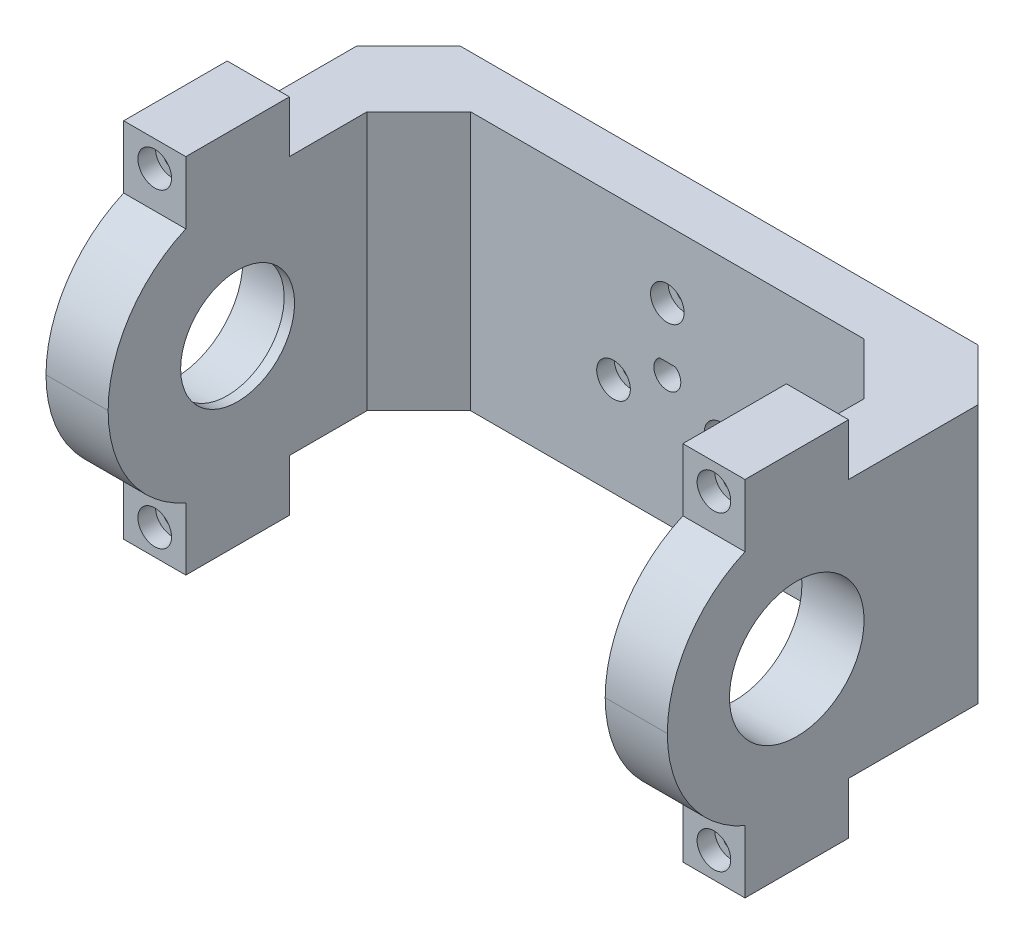
SolidWorks part; units mm, degrees
ref_plane "Ebene vorne" through (0, 0, 0) normal (0, 0, 1) x (1, 0, 0)
ref_plane "Ebene oben" through (0, 0, 0) normal (0, 1, 0) x (1, 0, 0)
ref_plane "Ebene rechts" through (0, 0, 0) normal (1, 0, 0) x (0, 0, -1)
sketch "Skizze1" plane through (0, 0, 0) normal (0, 1, 0) x (1, 0, 0)
  line L0 (-60, 0) -> (60, 0)
  line L5 (0, 0) -> (0, -46.899) construction
  line L6 (-60, 0) -> (-60, -70)
  line L7 (-60, -70) -> (-48, -70)
  line L8 (-48, -70) -> (-48, -10)
  line L9 (-48, -10) -> (48, -10)
  line L10 (48, -10) -> (48, -70)
  line L11 (48, -70) -> (60, -70)
  line L12 (60, -70) -> (60, 0)
  point P4 (0, 0)
  dimension "D1" = 120
  dimension "D2" = 10
  dimension "D3" = 12
  dimension "D4" = 70
extrude "Aufsatz-Linear austragen1" add sketch "Skizze1" along normal mid plane 50
sketch "Skizze2" plane through (0, 0, 0) normal (0, 0, -1) x (-1, 0, 0)
  line L0 (-1.533, 2.1) -> (1.533, 2.1)
  arc A0 (-1.533, 2.1) -> (1.533, 2.1) centre (0, 0) ccw
  dimension "D1" = 5.2
  dimension "D2" = 4.7
extrude "Schnitt-Linear austragen1" cut sketch "Skizze2" against normal blind 20
chamfer "Fase1" distance 10 angle 45 4 edges at (60, 0, 0) (48, 0, 10) (-60, 0, 0) (-48, 0, 10)
fillet "Verrundung1" radius 25 4 edges at (-54, -25, 70) (-54, 25, 70) (54, 25, 70) (54, -25, 70)
sketch "Skizze3" plane through (0, 0, 10) normal (0, 0, 1) x (1, 0, 0)
  line L0 (0, 0) -> (0, 12) construction
  circle A0 centre (0, 12) radius 3.25
  dimension "D2" = 6.5
  dimension "D1" = 12
extrude "Schnitt-Linear austragen2" cut sketch "Skizze3" against normal blind 3.4
sketch "Skizze4" plane through (0, 0, 6.6) normal (0, 0, 1) x (1, 0, 0)
  circle A0 centre (0, 12) radius 1.7
  dimension "D1" = 3.4
extrude "Schnitt-Linear austragen3" cut sketch "Skizze4" against normal up to surface (6.6 mm away) up to face at (0, -0.25, 0)
pattern_circular "Kreismuster1" count 3 over 360 about axis through (0, 0, 20) along (0, 0, -1) of "Schnitt-Linear austragen3", "Schnitt-Linear austragen2"
sketch "Skizze5" plane through (60, 0, 0) normal (1, 0, 0) x (0, 0, -1)
  line L0 (-45, 25) -> (-45, -25) construction
  line L2 (0, 0) -> (-70, 0) construction
  circle A0 centre (-45, 0) radius 13
  arc A2 (-70, 0) -> (-45, -25) centre (-45, 0) ccw construction
  point P5 (-70, 0)
  point P11 (-50, 0)
  dimension "D1" = 26
extrude "Schnitt-Linear austragen4" cut sketch "Skizze5" against normal through all
sketch "Skizze7" plane through (0, 25, 0) normal (0, 1, 0) x (1, 0, 0)
  line L0 (-60, -10) -> (-60, -45) construction
  line L1 (-60, -35) -> (-48, -35)
  line L2 (-60, -35) -> (-60, -55)
  line L3 (-60, -55) -> (-48, -55)
  line L4 (-48, -35) -> (-48, -55)
  line L5 (-48, -70) -> (-48, -45) construction
  line L7 (-62.3385, -45) -> (-41.5692, -45) construction
  line L8 (-60, -45) -> (-48, -45) construction
  point P12 (0, 0)
  dimension "D1" = 20
extrude "Aufsatz-Linear austragen2" add sketch "Skizze7" along normal blind 10 and the other way blind 10
sketch "Skizze9" plane through (0, 0, 35) normal (0, 0, 1) x (1, 0, 0)
  line L0 (-48, 30) -> (-60, 30) construction
  line L1 (-48, 25) -> (-48, 35) construction
  line L2 (-60, 25) -> (-60, 35) construction
  circle A0 centre (-54, 30) radius 1.7
  point P9 (-55, 30)
  dimension "D1" = 3.4
extrude "Schnitt-Linear austragen7" cut sketch "Skizze9" along normal through all
sketch "Skizze8" plane through (0, 0, 55) normal (0, 0, 1) x (1, 0, 0)
  circle A0 centre (-54, 30) radius 3.25
  circle A1 centre (-54, 30) radius 1.7 construction
  point P2 (-55.1693, 29.1455)
  point P3 (-54.6489, 29.8028)
  point P14 (0, 0)
  dimension "D1" = 6.5
extrude "Schnitt-Linear austragen6" cut sketch "Skizze8" against normal blind 3.4
sketch "Skizze10" plane through (-48, 0, 0) normal (-1, 0, 0) x (0, 0, 1)
  circle A0 centre (45, 0) radius 13
  circle A2 centre (45, 0) radius 13 construction
  circle A3 centre (45, 0) radius 11
  point P5 (50, 0)
  dimension "D1" = 22
extrude "Aufsatz-Linear austragen3" add sketch "Skizze10" along normal blind 2
mirror "Spiegeln1" about plane through (0, 0, 0) normal (1, 0, 0) of "Schnitt-Linear austragen6", "Schnitt-Linear austragen7", "Aufsatz-Linear austragen2" second plane through (0, 0, 0) second plane normal (0, 1, 0)
sketch "Skizze6" plane through (0, 0, 0) normal (0, 1, 0) x (1, 0, 0)
  line L0 (50, 0) -> (-50, 0) construction
  line L1 (-60, 0) -> (60, 0)
  line L2 (-60, 0) -> (-60, -45)
  line L3 (-60, -45) -> (60, -45)
  line L4 (60, 0) -> (60, -45)
  line L5 (-60, -10) -> (-60, -35) construction
  line L6 (60, -35) -> (60, -10) construction
  line L7 (48, -45) -> (60, -45) construction
extrude "Schnitt-Linear austragen5" [suppressed] cut sketch "Skizze6" against normal through all both and the other way through all flip side to cut
sketch "Skizze11" plane through (-60, 0, 0) normal (1, 0, 0) x (0, 0, -1)
  circle A0 centre (-45, 0) radius 17.5 construction
  circle A1 centre (-62.5, 0) radius 1.9
  dimension "D1" = 35
  dimension "D2" = 3.8
extrude "Schnitt-Linear austragen8" cut sketch "Skizze11" along normal blind 10
pattern_circular "Kreismuster2" count 4 over 360 about axis through (-60, 0, 45) along (1, 0, 0) of "Schnitt-Linear austragen8"
